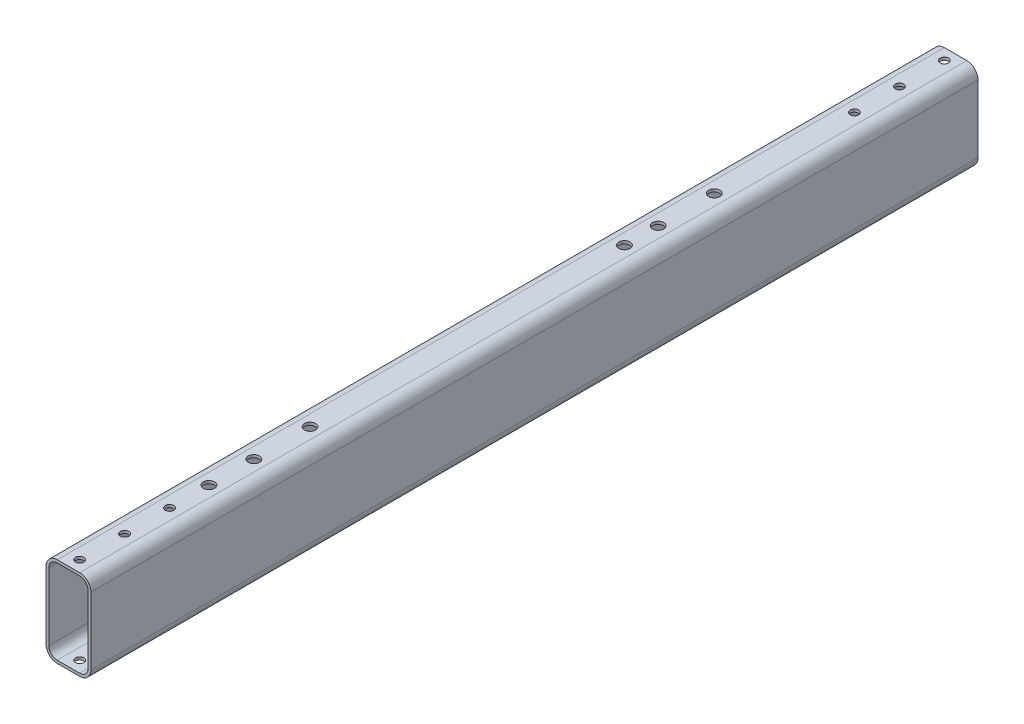
SolidWorks part; units mm, degrees
material "6061-T6 (SS)"
ref_plane "Front Plane" through (0, 0, 0) normal (0, 0, 1) x (1, 0, 0)
ref_plane "Top Plane" through (0, 0, 0) normal (0, 1, 0) x (1, 0, 0)
ref_plane "Right Plane" through (0, 0, 0) normal (1, 0, 0) x (0, 0, -1)
sketch "Sketch1" plane through (0, 0, 0) normal (0, 0, 1) x (1, 0, 0)
  line L1 (-6.35, -25.4) -> (6.35, -25.4)
  line L2 (-12.7, -19.05) -> (-12.7, 19.05)
  line L3 (-6.35, 25.4) -> (6.35, 25.4)
  line L4 (12.7, -19.05) -> (12.7, 19.05)
  line L5 (-12.7, -25.4) -> (12.7, 25.4) construction
  line L6 (-12.7, 25.4) -> (12.7, -25.4) construction
  arc A0 (-12.7, -19.05) -> (-6.35, -25.4) centre (-6.35, -19.05) ccw
  arc A1 (6.35, -25.4) -> (12.7, -19.05) centre (6.35, -19.05) ccw
  arc A2 (6.35, 25.4) -> (12.7, 19.05) centre (6.35, 19.05) cw
  arc A3 (-12.7, 19.05) -> (-6.35, 25.4) centre (-6.35, 19.05) cw
  point P0 (0, 0)
  dimension "D3" = 6.35
  dimension "D1" = 50.8
  dimension "D2" = 25.4
extrude "Extrude-Thin1" add sketch "Sketch1" along normal blind 501.65 thin thin type one direction reverse wall 1.5875
hole_wizard "3/16 (0.1875) Diameter Hole1" positions "3DSketch1" profile "Sketch3" hole size "3/16" standard "ANSI Inch" end condition through all
sketch3d "3DSketch1"
  line L1 (6.35, 25.4, 0) -> (-6.35, 25.4, 0) construction
  line L6 (0, 25.4, 501.65) -> (0, 25.4, 0) construction
  line L7 (6.35, 25.4, 501.65) -> (-6.35, 25.4, 501.65) construction
  point P57 (0, 25.4, 6.35)
  point P59 (0, 25.4, 31.75)
  point P61 (0, 25.4, 57.15)
  point P63 (0, 25.4, 469.9)
  point P65 (0, 25.4, 444.5)
  point P67 (0, 25.4, 495.3)
  dimension "D1" = 25.4
  dimension "D2" = 25.4
  dimension "D3" = 6.35
  dimension "D4" = 25.4
  dimension "D5" = 25.4
  dimension "D6" = 6.35
sketch "Sketch3" plane through (0, 25.4, 495.3) normal (1, 0, 0) x (0, 0, 1)
  line L0 (0, 0) -> (0, 50.8)
  line L1 (0, 50.8) -> (2.3812, 50.8)
  line L2 (2.3812, 50.8) -> (2.3812, 0)
  line L5 (2.3812, 0) -> (0, 0)
  line L11 (0, -6.35) -> (0, 107.95) construction
  dimension "Thru Hole Dia." = 4.7625
  dimension "Thru Hole Depth" = 50.8
hole_wizard "3/16 (0.195) Diameter Hole1" positions "Sketch4" profile "Sketch5" hole size "3/16" standard "ANSI Inch" end condition up to next
sketch "Sketch4" plane through (0, -25.4, 0) normal (0, -1, 0) x (-1, 0, 0)
  point P74 (-3.175, -85.725)
  point P78 (3.175, -111.125)
  point P81 (-3.175, -136.525)
  point P84 (3.175, -161.925)
  point P87 (-3.175, -187.325)
  point P90 (3.175, -212.725)
  point P93 (-3.175, -238.125)
  point P96 (3.175, -263.525)
  point P99 (-3.175, -288.925)
  point P102 (3.175, -314.325)
  point P105 (-3.175, -339.725)
  point P108 (3.175, -365.125)
  point P111 (3.175, -415.925)
  point P114 (-3.175, -390.525)
sketch "Sketch5" plane through (3.175, -25.4, 85.725) normal (1, 0, 0) x (0, 0, -1)
  line L0 (0, 0) -> (0, 1.5875)
  line L1 (0, 1.5875) -> (2.4765, 1.5875)
  line L2 (2.4765, 1.5875) -> (2.4765, 0)
  line L5 (2.4765, 0) -> (0, 0)
  line L11 (0, -6.35) -> (0, 107.95) construction
  dimension "Thru Hole Dia." = 4.953
  dimension "Thru Hole Depth" = 1.5875
hole_wizard "1/4 (0.25) Diameter Hole1" positions "Sketch6" profile "Sketch7" hole size "1/4" standard "ANSI Inch"
sketch "Sketch6" plane through (0, 25.4, 0) normal (0, 1, 0) x (1, 0, 0)
  point P0 (0, -187.2327)
  point P3 (0, -136.4252)
  point P6 (0, -168.1752)
  point P9 (0, -396.8)
  point P12 (0, -365.05)
  point P15 (0, -422.2)
sketch "Sketch7" plane through (0, 25.4, 187.2327) normal (1, 0, 0) x (0, 0, 1)
  line L0 (0, 0) -> (0, 27.3077)
  line L1 (0, 27.3077) -> (3.175, 25.4)
  line L2 (3.175, 25.4) -> (3.175, 0)
  line L5 (3.175, 0) -> (0, 0)
  line L10 (0, 27.3077) -> (-3.175, 25.4) construction
  line L11 (0, -6.35) -> (0, 107.95) construction
  dimension "Hole Dia." = 6.35
  dimension "Hole Depth" = 25.4
  dimension "Drill Angle" = 118
